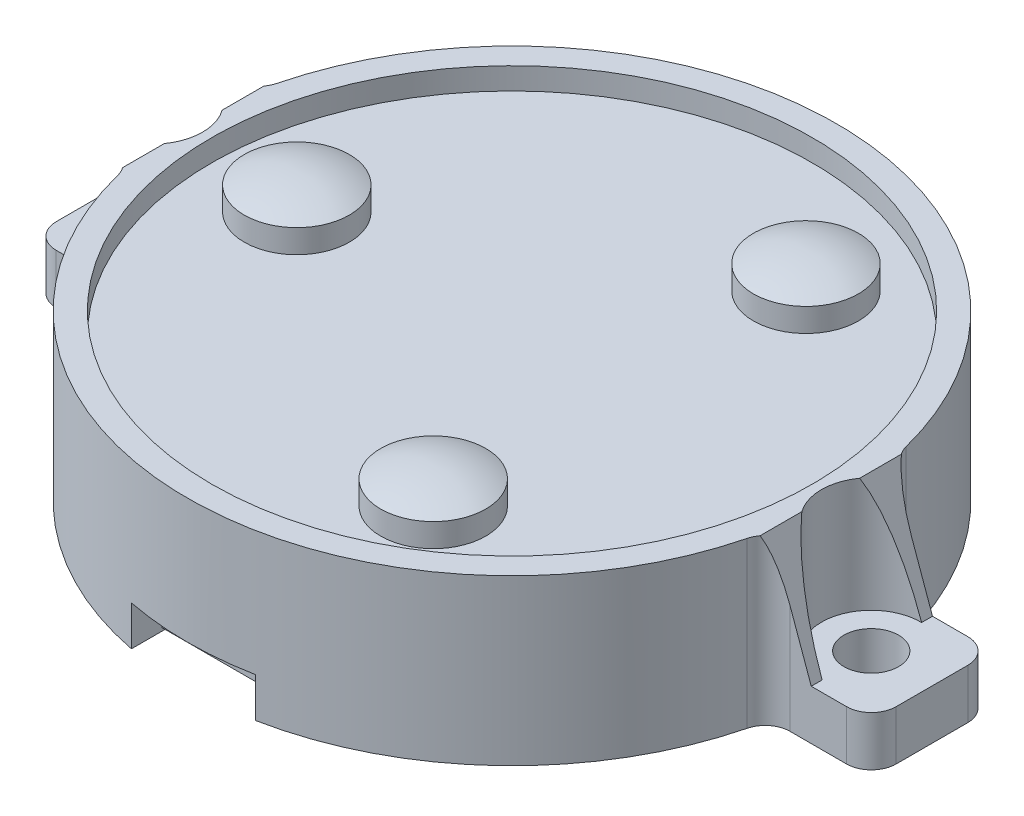
SolidWorks part; units mm, degrees
ref_plane "Front Plane" through (0, 0, 0) normal (0, 0, 1) x (1, 0, 0)
ref_plane "Top Plane" through (0, 0, 0) normal (0, 1, 0) x (1, 0, 0)
ref_plane "Right Plane" through (0, 0, 0) normal (1, 0, 0) x (0, 0, -1)
sketch "Sketch1" plane through (0, 0, 0) normal (0, 1, 0) x (1, 0, 0)
  circle A0 centre (0, 0) radius 15.35
  dimension "D1" = 30.7
extrude "Boss-Extrude1" add sketch "Sketch1" along normal blind 2.71
sketch "Sketch2" plane through (0, 2.71, 0) normal (0, 1, 0) x (-1, 0, 0)
  line L1 (-5.5, 9.5263) -> (0, 0) construction
  line L2 (0, 3.3605) -> (0, -3.3605) construction
  circle A0 centre (-5.5, 9.5263) radius 2.685
  dimension "D1" = 5.37
  dimension "D2" = 11
  dimension "D3" = 30
extrude "Boss-Extrude2" add sketch "Sketch2" along normal blind 1.2
dome "Dome1" faces to dome 1 distance 0.6 reverse direction no elliptical dome no face at (5.5, 3.91, 12.2113) parameters "D1"=0.6
pattern_circular "CirPattern1" count 3 over 360 about axis through (0, 2.71, 0) along (0, 1, 0) of "Dome1", "Boss-Extrude2"
sketch "Sketch3" plane through (0, 0, 0) normal (0, -1, 0) x (1, 0, 0)
  line L0 (0, 15.35) -> (0, -15.35) construction
  line L2 (2.75, 15.15) -> (-2.75, 15.15)
  line L3 (2.75, 15.15) -> (2.75, 10.95)
  line L4 (2.75, 10.95) -> (-2.75, 10.95)
  line L5 (-2.75, 15.15) -> (-2.75, 10.95)
  line L6 (2.75, 15.15) -> (-2.75, 10.95) construction
  line L7 (2.75, 10.95) -> (-2.75, 15.15) construction
  line L8 (-2.75, 13.05) -> (4.4429, 13.05) construction
  line L9 (2.75, 14.45) -> (4.25, 14.45)
  line L10 (4.25, 14.45) -> (4.25, 11.65)
  line L11 (4.25, 11.65) -> (2.75, 11.65)
  line L12 (-4.25, 11.65) -> (-2.75, 11.65)
  line L13 (-4.25, 14.45) -> (-4.25, 11.65)
  line L14 (-2.75, 14.45) -> (-4.25, 14.45)
  line L15 (0, 0) -> (-15.35, 0) construction
  line L16 (2.75, -14.45) -> (4.25, -14.45)
  line L17 (4.25, -14.45) -> (4.25, -11.65)
  line L18 (4.25, -11.65) -> (2.75, -11.65)
  line L19 (2.75, -15.15) -> (2.75, -10.95)
  line L20 (2.75, -10.95) -> (-2.75, -10.95)
  line L21 (-4.25, -11.65) -> (-2.75, -11.65)
  line L22 (-4.25, -14.45) -> (-4.25, -11.65)
  line L23 (-2.75, -14.45) -> (-4.25, -14.45)
  line L24 (-2.75, -15.15) -> (-2.75, -10.95)
  line L25 (2.75, -15.15) -> (-2.75, -15.15)
  line L26 (-1.5955, 10.95) -> (-1.5955, 0) construction
  line L27 (-1.5955, 0) -> (-1.5955, -10.95) construction
  point P4 (0, 13.05)
  point P16 (4.25, 13.05)
  circle M1 centre (0, 0) radius 15.35
  dimension "D1" = 5.5
  dimension "D3" = 4.2
  dimension "D4" = 2.8
  dimension "D5" = 1.5
  dimension "D6" = 21.9
extrude "Boss-Extrude3" add sketch "Sketch3" along normal blind 2.55 contours L2 L5 L4 L3 | L25 L19 L20 L24 | L11 L10 L9 L3 | L5 L14 L13 L12 | L19 L16 L17 L18 | L23 L24 L21 L22 | L3 L2 M1 | L2 L5 M1 | L25 L24 M1 | L25 L19 M1 region at (2.6575, 0, 15.134) region at (0, 0, 13.0488) region at (-2.6575, 0, 15.134) region at (3.5, 0, 13.05) region at (0, 0, -13.0488) region at (2.6575, 0, -15.134) region at (-3.5, 0, 13.05) region at (-2.6575, 0, -15.134) region at (3.5, 0, -13.05) region at (-3.5, 0, -13.05)
sketch "Sketch4" plane through (0, -2.55, 0) normal (0, -1, 0) x (1, 0, 0)
  line L0 (2.75, 10.95) -> (-2.75, 10.95) construction
  line L1 (2.75, 15.15) -> (-2.75, 15.15) construction
  line L2 (2.75, 10.95) -> (-2.75, 10.95)
  line L3 (2.75, 15.15) -> (-2.75, 15.15)
  line L4 (2.75, 15.15) -> (2.75, 10.95)
  line L5 (-2.75, 10.95) -> (-2.75, 15.15)
  line L6 (2.75, -15.15) -> (2.75, -10.95)
  line L7 (2.75, -10.95) -> (-2.75, -10.95)
  line L8 (-2.75, -10.95) -> (-2.75, -15.15)
  line L9 (-2.75, -15.15) -> (2.75, -15.15)
  line L10 (2.75, -15.15) -> (2.7698, -15.1661)
  line M2 (-2.75, 15.15) -> (-2.75, 14.45)
  line M6 (-2.75, 11.65) -> (-2.75, 10.95)
  line M7 (-2.75, 10.95) -> (2.75, 10.95)
  line M8 (2.75, 10.95) -> (2.75, 11.65)
  line M12 (2.75, 14.45) -> (2.75, 15.15)
  line M14 (2.75, 15.15) -> (-2.75, 15.15)
extrude "Boss-Extrude4" add sketch "Sketch4" along normal blind 1.44 contours L5 L4 M6 M7 M8 M12 M14 M2 | L8 L9 L6 L7 region at (0, -2.55, 13.05) region at (0, -2.55, -13.05)
sketch "Sketch5" plane through (0, 0, 0) normal (0, -1, 0) x (1, 0, 0)
  line L0 (-5.1644, -9.426) -> (-2.0166, -2.879)
  line L1 (-2.0166, -2.879) -> (-8.0142, 0.0047)
  line L2 (-8.0142, 0.0047) -> (-11.162, -6.5423)
  line L3 (-11.162, -6.5423) -> (-5.1644, -9.426)
  line L4 (-4.25, -14.45) -> (-4.25, -11.65) construction
  line L5 (-5.1644, -9.426) -> (-5.1644, -14.4552) construction
  line L8 (-2.0166, -2.879) -> (15.0776, -2.879) construction
  arc A0 (-2.75, 15.1017) -> (-2.75, -15.1017) centre (0, 0) ccw construction
  arc A1 (2.75, -15.1017) -> (2.75, 15.1017) centre (0, 0) ccw construction
  dimension "D1" = 6.6548
  dimension "D2" = 7.2644
  dimension "D3" = 5.0292
  dimension "D4" = 0.9144
  dimension "D5" = 17.0942
extrude "Chip" add sketch "Sketch5" along normal blind 1.7018
sketch "Sketch6" plane through (0, -2.55, 0) normal (0, -1, 0) x (1, 0, 0)
  line L0 (-3.175, 16.2795) -> (-3.175, 10.525)
  line L1 (-3.175, 10.525) -> (3.175, 10.525)
  line L2 (3.175, 10.525) -> (3.175, 16.2795)
  line L3 (-3.175, 14.7504) -> (-2.75, 14.7504) construction
  line L4 (-2.75, 15.1017) -> (-2.75, 14.45) construction
  line L5 (1.1597, 10.95) -> (1.1597, 10.525) construction
  line L6 (2.75, 15.1017) -> (2.75, 14.45) construction
  line L7 (2.75, 14.7758) -> (3.175, 14.7758) construction
  line L8 (2.75, 10.95) -> (-2.75, 10.95) construction
  line L9 (-16.5862, 0) -> (16.5862, 0) construction
  line L10 (3.175, -10.525) -> (3.175, -16.2795)
  line L11 (-3.175, -10.525) -> (3.175, -10.525)
  line L12 (-3.175, -16.2795) -> (-3.175, -10.525)
  arc A0 (3.175, -16.2795) -> (3.175, 16.2795) centre (0, 0) ccw
  arc A4 (-3.175, 16.2795) -> (-3.175, -16.2795) centre (0, 0) ccw
  dimension "D1" = 33.1724
  dimension "D2" = 6.35
extrude "Boss-Extrude5" add sketch "Sketch6" along normal blind 2.032
sketch "Sketch7" plane through (0, -2.55, 0) normal (0, 1, 0) x (1, 0, 0)
  arc A0 (-2.75, 15.1017) -> (-2.75, -15.1017) centre (0, 0) ccw construction
  arc A1 (-2.75, 15.1017) -> (-2.75, -15.1017) centre (0, 0) ccw construction
  circle A2 centre (0, 0) radius 15.35
  circle A3 centre (0, 0) radius 16.5862
  arc A5 (3.175, -16.2795) -> (3.175, 16.2795) centre (0, 0) ccw construction
extrude "Boss-Extrude6" add sketch "Sketch7" along normal blind 6.3779
sketch "Sketch8" plane through (0, -4.582, 0) normal (0, -1, 0) x (1, 0, 0)
  line L0 (-16.2942, 3.0988) -> (-21.4693, 3.0988)
  line L1 (-21.4693, 3.0988) -> (-21.4693, -3.0988)
  line L2 (-21.4693, -3.0988) -> (-16.2942, -3.0988)
  line L3 (-16.1802, 3.0988) -> (-16.1802, 0) construction
  line L4 (-16.1802, 0) -> (-16.1802, -3.0988) construction
  line L5 (0, 16.5862) -> (0, -16.5862) construction
  line L6 (21.4694, -3.0988) -> (16.2942, -3.0988)
  line L7 (21.4693, 3.0988) -> (21.4694, -3.0988)
  line L8 (16.2942, 3.0988) -> (21.4693, 3.0988)
  line L9 (-19.7612, 0) -> (-19.7612, 7.919) construction
  line L10 (19.7612, 0) -> (19.7612, 7.1097) construction
  line L11 (-16.9672, 0) -> (-16.9672, 14.8047) construction
  line L12 (16.9672, 0) -> (16.9672, 17.6126) construction
  arc A0 (-3.175, 16.2795) -> (-3.175, -16.2795) centre (0, 0) ccw construction
  arc A1 (-16.2942, 3.0988) -> (-16.2942, -3.0988) centre (0, 0) ccw
  arc A2 (3.175, 16.2795) -> (-3.175, 16.2795) centre (0, 0) ccw construction
  arc A3 (-3.175, -16.2795) -> (3.175, -16.2795) centre (0, 0) ccw construction
  circle A4 centre (-18.3642, 0) radius 1.397
  circle A5 centre (18.3642, 0) radius 1.397
  arc M1 (-3.175, 16.2795) -> (-3.175, -16.2795) centre (0, 0) ccw
  arc M5 (3.175, -16.2795) -> (3.175, 16.2795) centre (0, 0) ccw
  dimension "D3" = 2.794
  dimension "D1" = 6.1976
  dimension "D2" = 42.9387
  dimension "D4" = 39.5224
extrude "Boss-Extrude7" add sketch "Sketch8" against normal up to surface (8.4099 mm away) contours L8 L6 L7 M5 | L1 L2 L0 M1 region at (-16.6669, -4.582, 0) region at (18.8818, -4.582, -3.0181) up to face at (0, 3.8279, 16.5862)
sketch "Sketch9" plane through (0, 3.8279, 0) normal (0, 1, 0) x (1, 0, 0)
  line L0 (-20.9085, 0) -> (-20.9085, 5.9767) construction
  line L2 (-15.8199, 0) -> (-15.8199, 4.4223) construction
  line L3 (-15.35, 0) -> (-15.35, 8.543) construction
  circle A0 centre (-18.3642, 0) radius 2.5443
  circle A1 centre (0, 0) radius 15.35 construction
  dimension "D1" = 0.4699
extrude "Cut-Extrude1" cut sketch "Sketch9" against normal blind 5.8699
sketch "Sketch10" plane through (0, 0, 3.0988) normal (0, 0, 1) x (1, 0, 0)
  line L0 (-21.4694, -2.042) -> (-18.396, -2.042)
  line L1 (-21.4694, 3.8279) -> (-21.4694, -4.582) construction
  line L4 (-16.2942, 3.8279) -> (-18.396, -2.042)
  line L6 (-21.4694, -2.042) -> (-21.4694, 3.8279)
  line L7 (-21.4694, 3.8279) -> (-16.2942, 3.8279)
  line L10 (-15.8199, -2.042) -> (-20.9085, -2.042) construction
  line L11 (-15.8199, -2.042) -> (-20.9085, -2.042) construction
  line M2 (-16.2942, 3.8279) -> (-21.4694, 3.8279)
  line M3 (-21.4694, 3.8279) -> (-21.4694, -4.582)
  dimension "D1" = 3.0734
extrude "Cut-Extrude4" cut sketch "Sketch10" against normal up to surface (6.1976 mm away) contours L4 L0 M2 M3 region at (-19.3626, 1.1423, 3.0988) up to face at (-18.8818, -0.377, -3.0988)
mirror "Mirror2" about plane through (0, 0, 0) normal (1, 0, 0) of "Cut-Extrude1", "Cut-Extrude4"
fillet "Fillet1" radius 1.27 8 edges at (-21.4693, -3.312, 3.0988) (-21.4693, -3.312, -3.0988) (-16.2942, -0.377, 3.0988) (-16.2942, -0.377, -3.0988) (16.2942, -0.377, -3.0988) (21.4694, -3.312, -3.0988) (21.4693, -3.312, 3.0988) (16.2942, -0.377, 3.0988)
